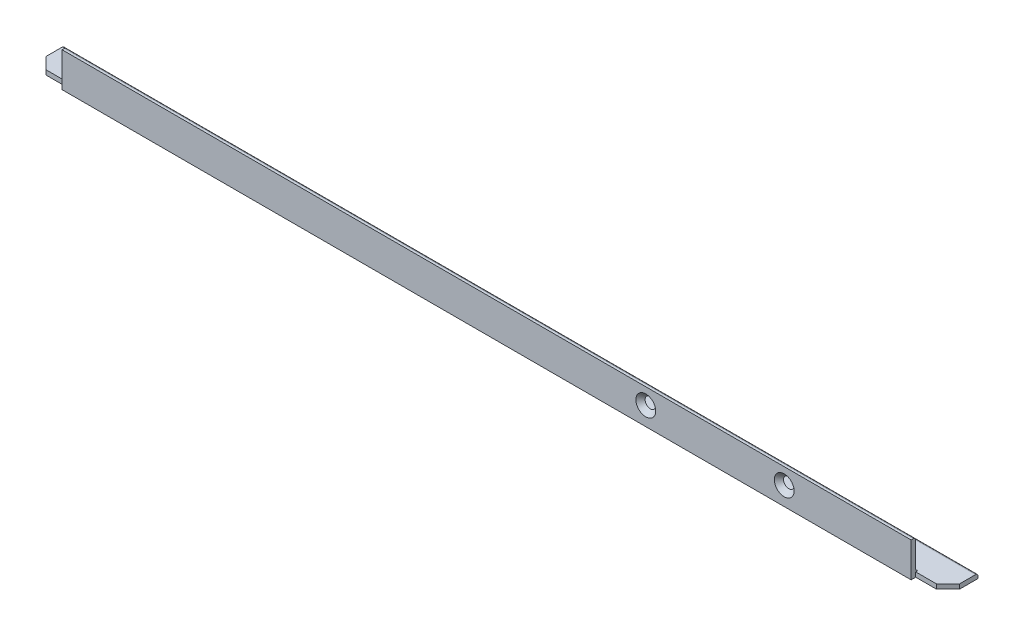
SolidWorks part; units mm, degrees
material "1060 Сплав"
ref_plane "Front" through (0, 0, 0) normal (0, 0, 1) x (1, 0, 0)
ref_plane "Top" through (0, 0, 0) normal (0, 1, 0) x (1, 0, 0)
ref_plane "Right" through (0, 0, 0) normal (1, 0, 0) x (0, 0, -1)
sketch "Эскиз1" plane through (0, 0, 0) normal (1, 0, 0) x (0, 0, -1)
  line L0 (0, 0) -> (0, 15)
  line L1 (0, 0) -> (15, 0)
  line L2 (0, 15) -> (1, 15)
  line L3 (2, 14) -> (2, 3)
  line L4 (3, 2) -> (14, 2)
  line L5 (15, 1) -> (15, 0)
  arc A0 (14, 2) -> (15, 1) centre (14, 1) cw
  arc A1 (1, 15) -> (2, 14) centre (1, 14) cw
  arc A2 (2, 3) -> (3, 2) centre (3, 3) ccw
  point P9 (15, 2)
  point P12 (2, 15)
  dimension "D5" = 1
  dimension "D1" = 15
  dimension "D2" = 15
  dimension "D3" = 2
  dimension "D4" = 2
extrude "Бобышка-Вытянуть1" add sketch "Эскиз1" along normal blind 396
sketch "Эскиз4" plane through (0, 0, 0) normal (0, -1, 0) x (1, 0, 0)
  line L0 (396, -15) -> (0, -15) construction
  line L1 (0, 0) -> (0, -15) construction
  line L2 (396, 0) -> (396, -15) construction
  circle A0 centre (371, -8) radius 2.25
  circle A1 centre (198, -8) radius 2.25
  circle A2 centre (25, -8) radius 2.25
  dimension "D1" = 4.5
  dimension "D2" = 7
  dimension "D3" = 25
  dimension "D4" = 4.5
  dimension "D5" = 25
  dimension "D6" = 7
  dimension "D7" = 173
  dimension "D8" = 4.5
extrude "Вырез-Вытянуть3" cut sketch "Эскиз4" against normal blind 2
chamfer "Фаска1" distance 2.05 angle 45 3 edges at (25, 0, -10.25) (371, 0, -10.25) (198, 0, -10.25)
sketch "Эскиз5" [suppressed] plane through (0, 2, 0) normal (0, 1, 0) x (1, 0, 0)
  line L0 (432, 14) -> (432, 3) construction
  line L1 (432, 15) -> (0, 15) construction
  line L2 (0, 14) -> (0, 3) construction
  circle A0 centre (392, 8) radius 2.3
  circle A1 centre (40, 8) radius 2.3
  dimension "D1" = 4.6
  dimension "D2" = 40
  dimension "D3" = 7
  dimension "D4" = 4.6
  dimension "D5" = 7
  dimension "D6" = 40
extrude "Вырез-Вытянуть4" [suppressed] cut sketch "Эскиз5" against normal through all
chamfer "Фаска3" [suppressed] distance 2.05 angle 45
sketch "Эскиз6" plane through (396, 0, 0) normal (1, 0, 0) x (0, 0, -1)
  line L0 (0, 0) -> (15, 0) construction
  line L1 (0, 15) -> (2, 15)
  line L2 (0, 15) -> (0, 0)
  line L3 (0, 0) -> (2, 0)
  line L4 (2, 0) -> (2, 2)
  line L5 (2, 2) -> (3, 2)
  line L6 (3, 2) -> (3, 15)
  line L7 (3, 15) -> (2, 15)
extrude "Вырез-Вытянуть5" cut sketch "Эскиз6" against normal blind 14
sketch "Эскиз7" plane through (0, 0, 0) normal (-1, 0, 0) x (0, 0, 1)
  line L0 (0, 0) -> (-15, 0) construction
  line L1 (0, 15) -> (-2, 15)
  line L2 (0, 15) -> (0, 0)
  line L3 (0, 0) -> (-2, 0)
  line L4 (-3, 2) -> (-2, 2)
  line L5 (-2, 2) -> (-2, 0)
  line L6 (-3, 2) -> (-3, 15)
  line L7 (-3, 15) -> (-2, 15)
extrude "Вырез-Вытянуть6" cut sketch "Эскиз7" against normal blind 14
sketch "Эскиз9" plane through (0, 2, 0) normal (0, 1, 0) x (1, 0, 0)
  line L0 (0, 2) -> (0, 7)
  line L1 (0, 14) -> (0, 2) construction
  line L2 (0, 7) -> (5, 2)
  line L3 (14, 2) -> (0, 2) construction
  line L4 (5, 2) -> (0, 2)
  line L5 (396, 2) -> (396, 7)
  line L6 (396, 14) -> (396, 2) construction
  line L7 (396, 7) -> (391, 2)
  line L8 (382, 2) -> (396, 2) construction
  line L9 (391, 2) -> (396, 2)
  dimension "D1" = 5
  dimension "D2" = 5
  dimension "D3" = 5
  dimension "D4" = 5
extrude "Вырез-Вытянуть7" cut sketch "Эскиз9" against normal through all
sketch "Эскиз10" plane through (0, 0, -2) normal (0, 0, -1) x (-1, 0, 0)
  line L0 (-382, 15) -> (-14, 15) construction
  line L1 (-14, 3) -> (-14, 14) construction
  circle A0 centre (-69, 8) radius 2.25
  circle A1 centre (-129, 8) radius 2.25
  dimension "D1" = 4.5
  dimension "D2" = 7
  dimension "D3" = 55
  dimension "D4" = 60
  dimension "D5" = 4.5
  dimension "D6" = 7
extrude "Вырез-Вытянуть8" [suppressed] cut sketch "Эскиз10" against normal through all
sketch "Эскиз11" plane through (0, 0, -2) normal (0, 0, -1) x (-1, 0, 0)
  line L0 (-382, 15) -> (-14, 15) construction
  line L1 (-382, 3) -> (-382, 14) construction
  circle A0 centre (-327, 8) radius 2.25
  circle A1 centre (-267, 8) radius 2.25
  dimension "D1" = 60
  dimension "D2" = 4.5
  dimension "D3" = 4.5
  dimension "D4" = 7
  dimension "D5" = 7
  dimension "D6" = 55
extrude "Вырез-Вытянуть9" cut sketch "Эскиз11" against normal through all
chamfer "Фаска4" [suppressed] distance 2.05 angle 45
chamfer "Фаска5" distance 2.05 angle 45 2 edges at (327, 10.25, 0) (267, 10.25, 0)
